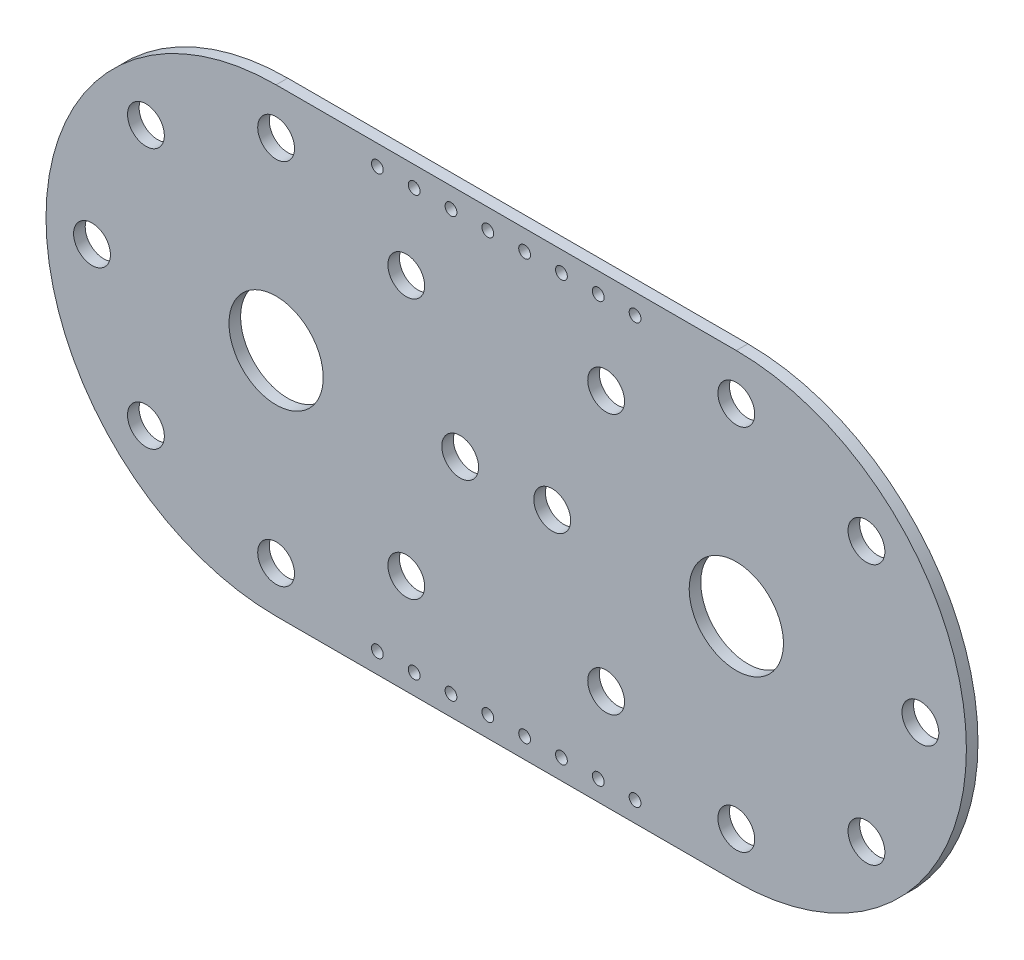
SolidWorks part; units mm, degrees
ref_plane "Front Plane" through (0, 0, 0) normal (0, 0, 1) x (1, 0, 0)
ref_plane "Top Plane" through (0, 0, 0) normal (0, 1, 0) x (1, 0, 0)
ref_plane "Right Plane" through (0, 0, 0) normal (1, 0, 0) x (0, 0, -1)
sketch "Sketch1" plane through (0, 0, 0) normal (0, 0, 1) x (1, 0, 0)
  line L0 (-15.875, 15.875) -> (47.625, 15.875) construction
  line L3 (0, 31.75) -> (31.75, 31.75)
  line L5 (0, 0) -> (31.75, 0)
  line L7 (15.875, 31.75) -> (15.875, 0) construction
  arc A40 (0, 31.75) -> (0, 0) centre (0, 15.875) ccw
  arc A41 (31.75, 0) -> (31.75, 31.75) centre (31.75, 15.875) ccw
  circle A42 centre (0, 15.875) radius 3.2512
  circle A43 centre (31.75, 15.875) radius 3.2512
  circle A44 centre (-12.7, 15.875) radius 1.27
  circle A45 centre (-8.9803, 24.8553) radius 1.27
  circle A46 centre (0, 28.575) radius 1.27
  circle A47 centre (8.9803, 24.8553) radius 1.27
  circle A48 centre (12.7, 15.875) radius 1.27
  circle A49 centre (8.9803, 6.8947) radius 1.27
  circle A50 centre (0, 3.175) radius 1.27
  circle A51 centre (-8.9803, 6.8947) radius 1.27
  circle A52 centre (31.75, 3.175) radius 1.27
  circle A53 centre (40.7303, 6.8947) radius 1.27
  circle A54 centre (22.7697, 6.8947) radius 1.27
  circle A55 centre (19.05, 15.875) radius 1.27
  circle A56 centre (22.7697, 24.8553) radius 1.27
  circle A57 centre (31.75, 28.575) radius 1.27
  circle A58 centre (40.7303, 24.8553) radius 1.27
  circle A59 centre (44.45, 15.875) radius 1.27
  point P29 (0, 15.875)
  dimension "D2" = 31.75
  dimension "D4" = 6.5024
  dimension "D5" = 12.7
  dimension "D6" = 8
  dimension "D1" = 31.75
  dimension "D3" = 6.5024
extrude "Boss-Extrude1" add sketch "Sketch1" along normal blind 0.8 contours L5 A41 L3 A40 A58 A56 A54 A52 A51 A50 A49 A48 A47 A46 A45 A44 A43 A42 A53 A55 A57 A59 region at (15.875, 15.875, 0)
sketch "Sketch3" plane through (0, 0, 0.8) normal (0, 0, -1) x (-1, 0, 0)
  line L0 (0, 0) -> (-31.75, 0) construction
  line L2 (0, 31.75) -> (-31.75, 31.75) construction
  line L3 (0, 0) -> (-31.75, 0)
  line L4 (0, 31.75) -> (-31.75, 31.75)
  line L5 (-15.875, 31.75) -> (-15.875, 0) construction
  line L6 (0, 15.875) -> (-33.3089, 15.875) construction
  circle A16 centre (-14.605, 30.353) radius 0.4064
  circle A17 centre (-12.065, 30.353) radius 0.4064
  circle A18 centre (-9.525, 30.353) radius 0.4064
  circle A19 centre (-6.985, 30.353) radius 0.4064
  circle A20 centre (-24.765, 30.353) radius 0.4064
  circle A21 centre (-22.225, 30.353) radius 0.4064
  circle A22 centre (-19.685, 30.353) radius 0.4064
  circle A23 centre (-17.145, 30.353) radius 0.4064
  circle A24 centre (-17.145, 1.397) radius 0.4064
  circle A25 centre (-19.685, 1.397) radius 0.4064
  circle A26 centre (-22.225, 1.397) radius 0.4064
  circle A27 centre (-24.765, 1.397) radius 0.4064
  circle A28 centre (-6.985, 1.397) radius 0.4064
  circle A29 centre (-9.525, 1.397) radius 0.4064
  circle A30 centre (-12.065, 1.397) radius 0.4064
  circle A31 centre (-14.605, 1.397) radius 0.4064
  dimension "D1" = 30.353
  dimension "D2" = 0.8128
  dimension "D3" = 1.27
extrude "Cut-Extrude3" cut sketch "Sketch3" along normal through all contours A19 | A18 | A17 | A16 | A23 | A22 | A21 | A20 | A28 | A29 | A30 | A31 | A24 | A25 | A26 | A27
